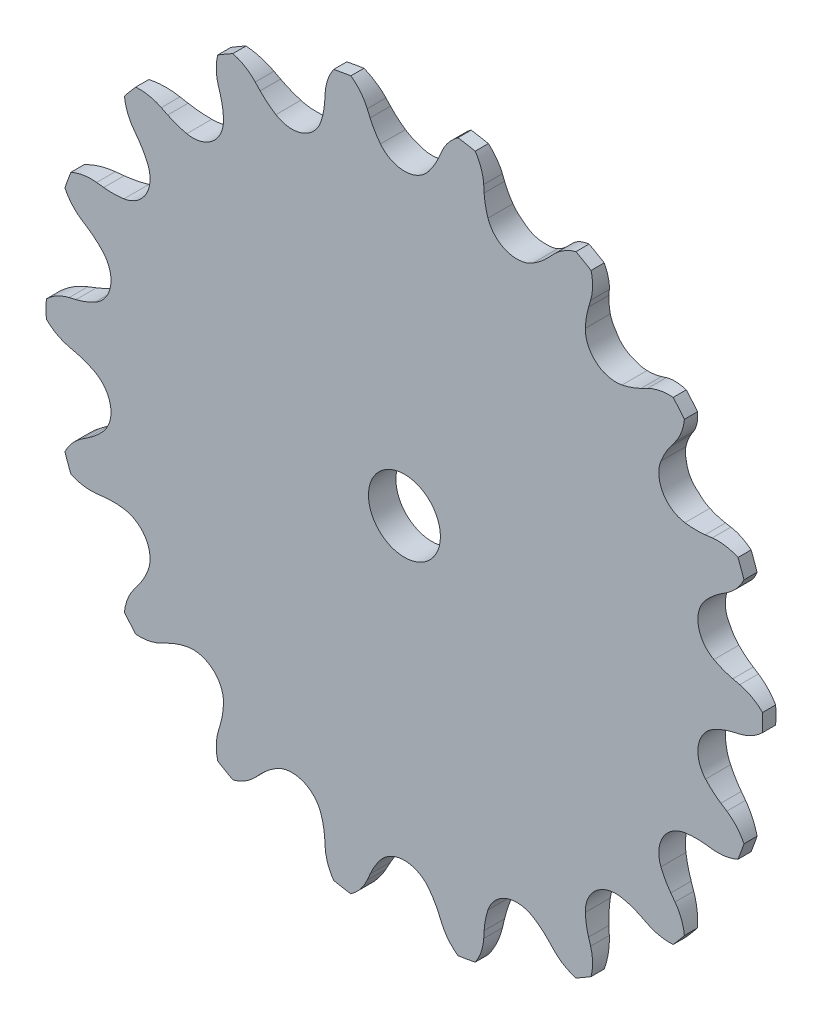
SolidWorks part; units mm, degrees
ref_plane "Front Plane" through (0, 0, 0) normal (0, 0, 1) x (1, 0, 0)
ref_plane "Top Plane" through (0, 0, 0) normal (0, 1, 0) x (1, 0, 0)
ref_plane "Right Plane" through (0, 0, 0) normal (1, 0, 0) x (0, 0, -1)
ref_axis "Axis1" through (0, 0, -88.99) along (0, 0, 1)
sketch "Sprocket-BaseSketch" plane through (0, 0, 0) normal (1, 0, 0) x (0, 0, -1)
  line L0 (1.397, 0) -> (1.397, 16.7363)
  line L1 (1.397, 16.7363) -> (0.6032, 19.9113)
  line L2 (0.6032, 19.9113) -> (-0.6032, 19.9113)
  line L3 (-0.6032, 19.9113) -> (-1.397, 16.7363)
  line L4 (-1.397, 16.7363) -> (-1.397, 0)
  line L5 (-1.397, 0) -> (1.397, 0)
  line L6 (5.588, 0) -> (-1.7463, 0) construction
  dimension "Hub Surface" = 1.397
  dimension "RightSide (1)" = 0.7938
  dimension "RightSide (2)" = 3.175
  dimension "OD" = 19.9113
  dimension "LeftSide (1)" = 0.7938
  dimension "LeftSide (2)" = 3.175
  dimension "Tooth Width" = 2.794
revolve "25 (04C) ANSI (ISO) Chain Number, 1.440in P.D." add sketch "Sprocket-BaseSketch" angle 360 about L6
sketch "Tooth-Sketch" plane through (0, 0, 0) normal (0, 0, 1) x (1, 0, 0)
  line L0 (0, 0) -> (0, 24.3788) construction
  line L1 (1.9086, 18.1962) -> (2.0662, 18.5596)
  line L2 (-1.9086, 18.1962) -> (-2.0662, 18.5596)
  line L3 (0, 18.2841) -> (6.2535, 17.1814) construction
  line L4 (0, 18.2841) -> (-6.2535, 17.1814) construction
  arc A0 (-1.3314, 17.2313) -> (1.3314, 17.2313) centre (0, 18.2841) ccw
  arc A1 (1.3314, 17.2313) -> (1.9086, 18.1962) centre (-2.0721, 19.9225) ccw
  arc A2 (-1.3314, 17.2313) -> (-1.9086, 18.1962) centre (2.0721, 19.9225) cw
  arc A3 (2.0662, 18.5596) -> (4.5526, 20.1914) centre (4.5526, 17.4814) cw
  arc A4 (-2.0662, 18.5596) -> (-4.5526, 20.1914) centre (-4.5526, 17.4814) ccw
  arc A5 (4.5526, 20.1914) -> (-4.5526, 20.1914) centre (0, 0) ccw
extrude "Tooth-Cut, Number of teeth: 18" cut sketch "Tooth-Sketch" against normal through all and the other way through all
pattern_circular "Tooth Pattern, 18 / 18" count 18 every 20 about axis through (0, 0, -88.99) along (0, 0, 1) of "Tooth-Cut, Number of teeth: 18"
sketch "Sketch3" plane through (0, 0, 0) normal (1, 0, 0) x (0, 0, -1)
  line L0 (-9.906, 0) -> (9.906, 0) construction
  line L1 (1.397, 0) -> (1.397, 14.2875)
  line L2 (1.397, 14.2875) -> (11.303, 14.2875)
  line L3 (11.303, 14.2875) -> (11.303, 0)
  line L4 (11.303, 0) -> (1.397, 0)
  dimension "Hub Mounting" = 1.397
  dimension "Hub OD" = 14.2875
  dimension "Hub Width" = 9.906
sketch "Sketch4" plane through (0, 0, 0) normal (0, 0, 1) x (1, 0, 0)
  circle A0 centre (0, 0) radius 2
  dimension "D1" = 4
extrude "Cut-Extrude1" cut sketch "Sketch4" against normal through all and the other way through all
sketch "Sketch5" plane through (0, 0, 0) normal (0, 0, 1) x (1, 0, 0)
  circle A0 centre (0, 0) radius 19.9113
  dimension "D1" = 39.8226
sketch "Sketch7" plane through (0, 0, 1.397) normal (0, 0, 1) x (1, 0, 0)
  circle A0 centre (0, 0) radius 52.2549
extrude "Cut-Extrude2" cut sketch "Sketch7" against normal blind 1.27
equation "\"D1@Sketch5\" = \"OD@Sprocket-BaseSketch\"*2"
